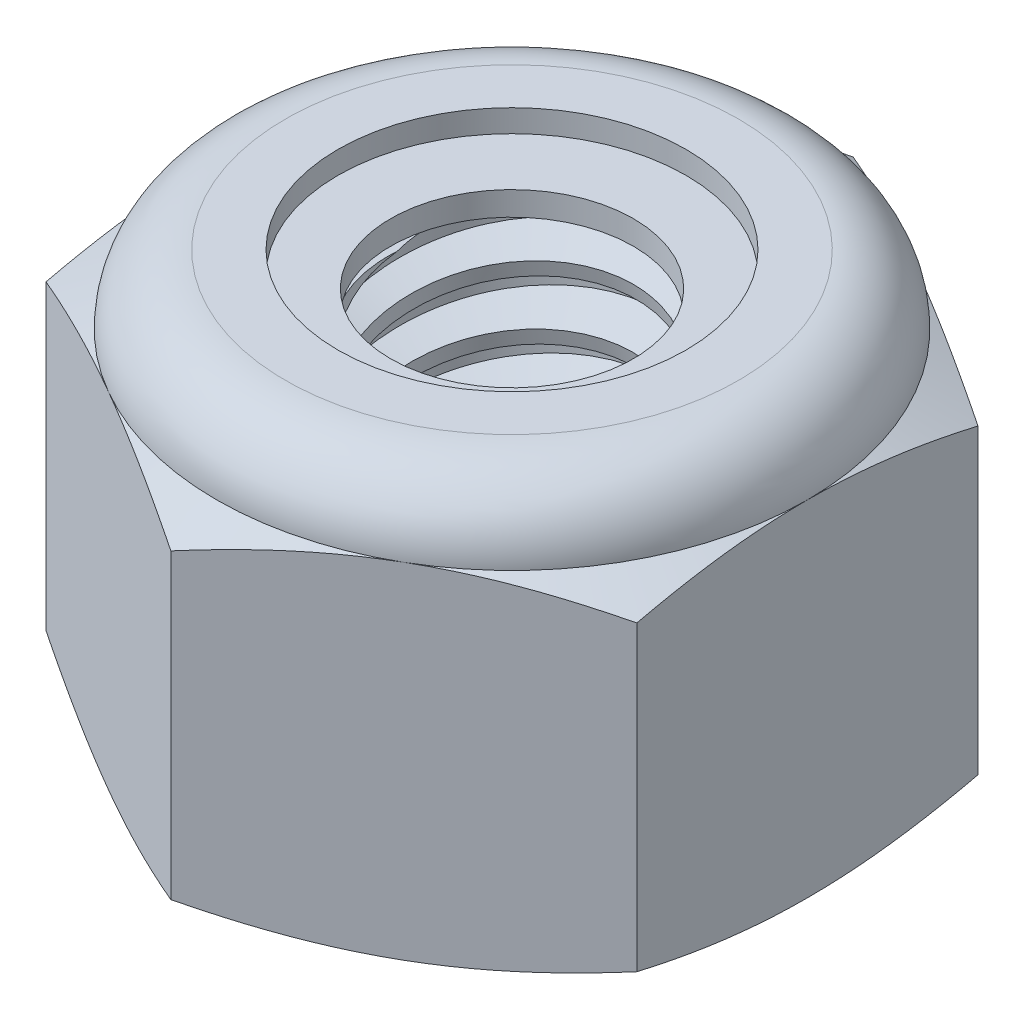
SolidWorks part; units mm, degrees
ref_plane "Front" through (0, 0, 0) normal (0, 0, 1) x (1, 0, 0)
ref_plane "Top" through (0, 0, 0) normal (0, 1, 0) x (1, 0, 0)
ref_plane "Right" through (0, 0, 0) normal (1, 0, 0) x (0, 0, -1)
sketch "Sketch1" plane through (0, 0, 0) normal (0, 1, 0) x (1, 0, 0)
  line L1 (0, 2.3094) -> (-2, 1.1547)
  line L2 (-2, 1.1547) -> (-2, -1.1547)
  line L3 (-2, -1.1547) -> (0, -2.3094)
  line L4 (0, -2.3094) -> (2, -1.1547)
  line L5 (2, -1.1547) -> (2, 1.1547)
  line L6 (2, 1.1547) -> (0, 2.3094)
  circle A0 centre (0, 0) radius 2 construction
  dimension "Hex Flats" = 4
extrude "Extrude1" add sketch "Sketch1" along normal blind 2.8
sketch "Sketch2" plane through (0, 0, 0) normal (1, 0, 0) x (0, 0, -1)
  line L0 (-1, 0) -> (-1, 2.8) construction
  line L1 (0, 0) -> (1, 0)
  line L2 (0, 0) -> (0, 2.8)
  line L3 (0, 2.8) -> (1, 2.8)
  line L4 (1, 0) -> (1, 2.8)
  line L5 (-1.1547, 2.8) -> (1.1547, 2.8) construction
  line L7 (0, -1) -> (0, 0) construction
  dimension "Thread Dia" = 2
revolve "Revolve1" add sketch "Sketch2" angle 360 about L7
sketch "Sketch3" plane through (0, 0, 0) normal (1, 0, 0) x (0, 0, -1)
  line L0 (1, 2.8) -> (-1, 2.8) construction
  line L1 (-1, 2.8) -> (-1, 2.4) construction
  line L2 (-1, 2.4) -> (1, 2.8) construction
  line L3 (1, 2.8) -> (1.0098, 2.751) construction
  line L4 (1.0098, 2.751) -> (1.0784, 2.4078)
  line L5 (1.0784, 2.4078) -> (0.8416, 2.4879)
  line L6 (0.8416, 2.4879) -> (0.822, 2.5859)
  line L7 (0.822, 2.5859) -> (1.0098, 2.751)
  line L8 (0.8318, 2.5369) -> (1.0441, 2.5794) construction
  line L9 (1, 2.8) -> (1, 2.5705) construction
  line L10 (1, 2.5705) -> (-1, 2.1705) construction
  line L11 (-1, 2.1705) -> (-1, 2.4) construction
  line L12 (-0.0859, 2.8) -> (0.0859, 1.9411) construction
  line L13 (-1, 0) -> (-1, 2.8) construction
  line L14 (0, 2.8) -> (1, 2.8) construction
  line L15 (1, 0) -> (1, 2.8) construction
  point P13 (0, 2.3705)
  dimension "D1" = 0.05
  dimension "D2" = 0.1
  dimension "Thread Pitch" = 0.4
  dimension "D4" = 60
  dimension "D5" = 0.4
revolve "Cut-Revolve1" cut sketch "Sketch3" angle 360 about L12
pattern_linear "LPattern1" count 7 spacing 0.4 along (0, -1, 0) count 2 spacing 0.4 along (0, 1, 0) of "Cut-Revolve1"
sketch "Sketch4" plane through (0, 0, 0) normal (1, 0, 0) x (0, 0, -1)
  line L0 (0, 2.8) -> (1, 2.8)
  line L1 (1, 2.8) -> (0.822, 2.717)
  line L2 (0.822, 2.717) -> (0.822, 0.083)
  line L3 (0.822, 0.083) -> (1, 0)
  line L4 (1, 0) -> (0, 0)
  line L5 (0, 0) -> (0, 2.8)
  line L6 (1, 0) -> (1, 2.8) construction
  line L7 (0, 2.8) -> (1, 2.8) construction
  line L8 (0, 0) -> (1, 0) construction
  line L9 (0, 0) -> (0, 2.8) construction
  line L10 (0, 2.8) -> (0, 2.9964) construction
  dimension "D1" = 25
revolve "Cut-Revolve2" cut sketch "Sketch4" angle 360 about L10
combine bodies "Combine1" operation type subtract main body 112 bodies to subtract 111
sketch "Sketch5" plane through (0, 0, 0) normal (1, 0, 0) x (0, 0, -1)
  line L0 (0, 0) -> (2, 0)
  line L1 (2, 0) -> (2.3094, 0.1443)
  line L2 (2.3094, 0.1443) -> (2.3094, 2.1891)
  line L3 (2.3094, 2.1891) -> (2, 2.3333)
  line L4 (1.5333, 2.8) -> (1.5333, 4.07)
  line L5 (1.5333, 4.07) -> (3.5794, 4.07)
  line L6 (3.5794, 4.07) -> (3.5794, -1.27)
  line L7 (3.5794, -1.27) -> (0, -1.27)
  line L8 (0, -1.27) -> (0, 0)
  line L9 (2, 2.3333) -> (2, 0) construction
  line L10 (0, 0) -> (1, 0) construction
  line L13 (2.3094, 1.1667) -> (3.5794, 1.1667) construction
  line L14 (2.3094, 2.8) -> (2.3094, 0) construction
  line L15 (0, 0) -> (0, 4.07) construction
  line L20 (0, 4.07) -> (1.5333, 4.07) construction
  line L22 (0, 2.8) -> (1, 2.8) construction
  arc A0 (2, 2.3333) -> (1.5333, 2.8) centre (1.5333, 2.3333) ccw
  dimension "D1" = 25
  dimension "D2" = 1.27
  dimension "D3" = 2.8
  dimension "D4" = 0.4667
revolve "Cut-Revolve3" cut sketch "Sketch5" angle 360 about L15
sketch "Sketch6" plane through (0, 0, 0) normal (1, 0, 0) x (0, 0, -1)
  line L0 (0, 2.3333) -> (1.8476, 2.3333)
  line L1 (1.5333, 2.6476) -> (1.1777, 2.6476)
  line L2 (0, 4.07) -> (0, 2.3333)
  line L3 (1.1777, 4.07) -> (0, 4.07)
  line L4 (0, 4.07) -> (1.5333, 4.07) construction
  line L5 (0, 0) -> (0, 4.07) construction
  line L6 (0, 4.07) -> (0, 44.323) construction
  line L7 (1.1777, 2.6476) -> (1.1777, 4.07)
  line L8 (1.5333, 2.8) -> (1.5333, 2.6476) construction
  line L9 (1.1777, 2.6476) -> (0.822, 2.6476) construction
  line L10 (0.822, 2.6476) -> (0.822, 2.717) construction
  arc A0 (1.8476, 2.3333) -> (1.5333, 2.6476) centre (1.5333, 2.3333) ccw
  arc A1 (2, 2.3333) -> (1.5333, 2.8) centre (1.5333, 2.3333) ccw construction
  dimension "D1" = 0.1524
revolve "Cut-Revolve4" cut sketch "Sketch6" angle 360 about L6
sketch "Sketch7" plane through (0, 0, 0) normal (1, 0, 0) x (0, 0, -1)
  line L0 (0.822, 2.4095) -> (1.7589, 2.4095)
  line L1 (1.5333, 2.5714) -> (0.822, 2.5714)
  line L2 (0.822, 2.5714) -> (0.822, 2.4095)
  line L3 (0.822, 2.4095) -> (0, 2.4095) construction
  line L4 (0, 2.4095) -> (0, 2.5714) construction
  line L5 (0, 2.5714) -> (0.822, 2.5714) construction
  line L6 (0.822, 2.4095) -> (0.822, 2.3333) construction
  line L7 (0, 2.3333) -> (1.8476, 2.3333) construction
  line L8 (1.5333, 2.5714) -> (1.5333, 2.6476) construction
  arc A0 (1.7589, 2.4095) -> (1.5333, 2.5714) centre (1.5333, 2.3333) ccw
  arc A2 (1.8476, 2.3333) -> (1.5333, 2.6476) centre (1.5333, 2.3333) ccw construction
  dimension "D1" = 0.0762
revolve "Revolve2" add sketch "Sketch7" angle 360 about L4
equation "\"D1@Sketch3\"=\"Thread Pitch@Sketch3\"/8"
equation "\"D2@Sketch3\"=\"Thread Pitch@Sketch3\"/4"
equation "\"D5@Sketch3\"=\"Thread Pitch@Sketch3\""
equation "\"D4@LPattern1\"=\"Thread Pitch@Sketch3\""
equation "\"D3@LPattern1\"=\"Thread Pitch@Sketch3\""
equation "\"D1@LPattern1\"=\"Height@Extrude1\"/\"Thread Pitch@Sketch3\""
equation "\"D4@Sketch5\"=\"Height@Extrude1\"/6"
